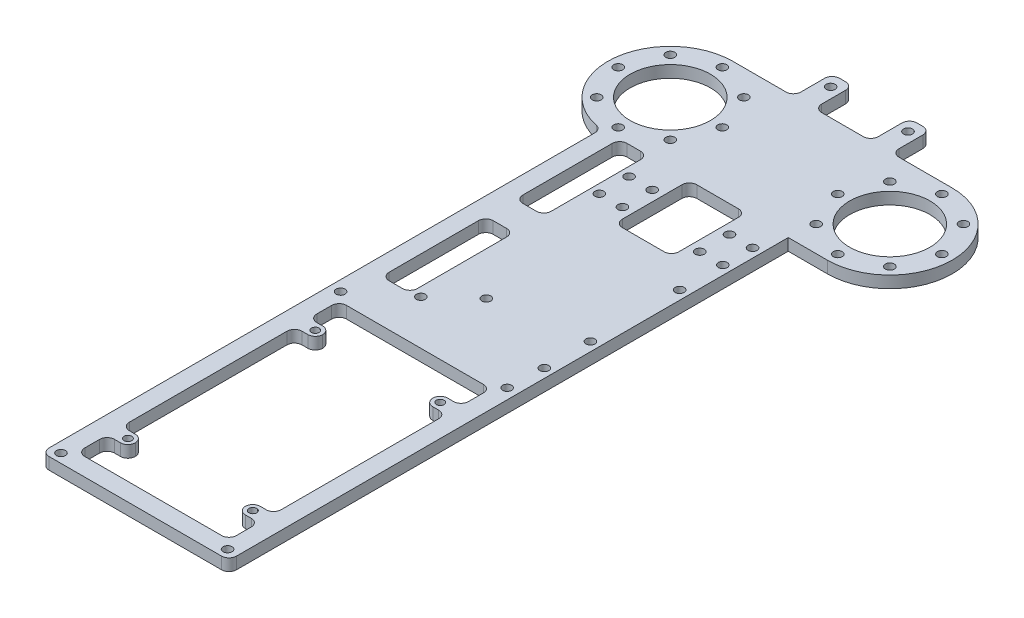
SolidWorks part; units mm, degrees
material "Thornel Mat VMA"
ref_plane "前视基准面" through (0, 0, 0) normal (0, 0, 1) x (1, 0, 0)
ref_plane "上视基准面" through (0, 0, 0) normal (0, 1, 0) x (1, 0, 0)
ref_plane "右视基准面" through (0, 0, 0) normal (1, 0, 0) x (0, 0, -1)
sketch "草图1" plane through (0, 0, 0) normal (0, 1, 0) x (1, 0, 0)
  line L0 (0, 0) -> (0, 103.5) construction
  line L1 (16.5, 103.5) -> (-16.5, 103.5)
  line L2 (-16.5, 103.5) -> (-16.5, 90.5)
  line L3 (-16.5, 90.5) -> (-36.9, 90.5)
  line L5 (-39.25, 48.6319) -> (-39.25, -39.5)
  line L6 (36.9, 48.5) -> (23.75, 48.5)
  line L7 (16.5, 90.5) -> (36.9, 90.5)
  line L8 (16.5, 103.5) -> (16.5, 90.5)
  line L9 (-13, 99.5) -> (-13, 39.5) construction
  line L10 (-36.9, 69.5) -> (-13, 69.5) construction
  line L11 (0, 0) -> (-39.25, 0) construction
  line L12 (-13, 39.5) -> (-13, 29.5) construction
  line L13 (-39.25, 24.5) -> (0, 24.5) construction
  line L14 (0, 0) -> (23.75, 0) construction
  line L15 (23.75, 34.5) -> (52.65, 34.5) construction
  line L16 (23.75, 34.5) -> (23.75, -34.5)
  line L17 (23.75, -34.5) -> (52.65, -34.5) construction
  line L18 (52.65, 34.5) -> (52.65, -34.5) construction
  line L19 (36.9, 39.5) -> (36.9, 34.5) construction
  line L20 (23.75, 48.5) -> (23.75, 34.5)
  line L21 (23.75, -34.5) -> (23.75, -39.5)
  line L23 (23.75, -39.5) -> (23.75, -139.5)
  line L24 (23.75, -139.5) -> (-39.25, -139.5)
  line L25 (-39.25, -139.5) -> (-39.25, -39.5)
  line L27 (-39.25, -39.5) -> (23.75, -39.5) construction
  line L28 (-7.75, -39.5) -> (-7.75, -139.5) construction
  line L29 (-39.25, -89.5) -> (-7.75, -89.5) construction
  line L30 (13, 39.5) -> (20.75, 39.5) construction
  line L31 (20.75, 39.5) -> (20.75, 29.5) construction
  line L32 (20.75, 29.5) -> (13, 29.5) construction
  line L33 (20.75, 29.5) -> (20.75, -30.5) construction
  arc A0 (-36.9, 90.5) -> (-39.25, 48.6319) centre (-36.9, 69.5) ccw
  arc A1 (36.9, 90.5) -> (36.9, 48.5) centre (36.9, 69.5) cw
  circle A2 centre (-36.9, 69.5) radius 13.5
  circle A3 centre (-36.9, 69.5) radius 17.5 construction
  circle A4 centre (-36.9, 87) radius 1.5
  circle A5 centre (-24.5256, 81.8744) radius 1.5
  circle A6 centre (-19.4, 69.5) radius 1.5
  circle A7 centre (-24.5256, 57.1256) radius 1.5
  circle A8 centre (-36.9, 52) radius 1.5
  circle A9 centre (-49.2744, 57.1256) radius 1.5
  circle A10 centre (-54.4, 69.5) radius 1.5
  circle A11 centre (-49.2744, 81.8744) radius 1.5
  circle A12 centre (-13, 99.5) radius 1.5
  circle A13 centre (-13, 39.5) radius 1.5
  circle A14 centre (-36.9, 69.5) radius 30 construction
  circle A15 centre (13, 39.5) radius 1.5
  circle A16 centre (13, 99.5) radius 1.5
  circle A17 centre (54.4, 69.5) radius 1.5
  circle A18 centre (49.2744, 57.1256) radius 1.5
  circle A19 centre (36.9, 52) radius 1.5
  circle A20 centre (24.5256, 57.1256) radius 1.5
  circle A21 centre (19.4, 69.5) radius 1.5
  circle A22 centre (24.5256, 81.8744) radius 1.5
  circle A23 centre (36.9, 87) radius 1.5
  circle A24 centre (49.2744, 81.8744) radius 1.5
  circle A25 centre (36.9, 69.5) radius 13.5
  circle A26 centre (-13, 29.5) radius 1.5
  circle A27 centre (36.9, 69.5) radius 30 construction
  circle A28 centre (-35.75, -42.5) radius 1.5
  circle A29 centre (-35.75, -136.5) radius 1.5
  circle A30 centre (20.25, -136.5) radius 1.5
  circle A31 centre (20.25, -42.5) radius 1.5
  circle A32 centre (13, 29.5) radius 1.5
  circle A33 centre (20.75, 15) radius 1.5
  circle A34 centre (20.75, -15) radius 1.5
  circle A35 centre (-28.75, -58) radius 1.3
  circle A36 centre (-28.75, -121) radius 1.3
  circle A37 centre (13.25, -121) radius 1.3
  circle A38 centre (13.25, -58) radius 1.3
  circle A39 centre (-9.25, -20) radius 1.5
  circle A40 centre (20.75, 39.5) radius 1.5
  circle A41 centre (-20.75, 39.5) radius 1.5
  circle A42 centre (20.75, 29.5) radius 1.5
  circle A43 centre (-20.75, 29.5) radius 1.5
  circle A44 centre (20.75, -30.5) radius 1.5
  circle A45 centre (-20.75, -30.5) radius 1.5
  point P37 (-36.9, 69.5)
  point P113 (0, 0)
  point P120 (0, 0)
  dimension "D2" = 27
  dimension "D3" = 3
  dimension "D5" = 35
  dimension "D6" = 60
  dimension "D7" = 3
  dimension "D9" = 26
  dimension "D10" = 4
  dimension "D12" = 10
  dimension "D13" = 5
  dimension "D21" = 3
  dimension "D22" = 94
  dimension "D23" = 56
  dimension "D24" = 3
  dimension "D25" = 30
  dimension "D26" = 3
  dimension "D27" = 21
  dimension "D19" = 42
  dimension "D29" = 63
  dimension "D30" = 2.6
  dimension "D31" = 5
  dimension "D32" = 30
  dimension "D33" = 3
  dimension "D34" = 3
  dimension "D1" = 73.8
  dimension "D8" = 60
  dimension "D11" = 33
  dimension "D14" = 5
  dimension "D15" = 69
  dimension "D16" = 28.9
  dimension "D17" = 5
  dimension "D18" = 100
  dimension "D20" = 52.65
  dimension "D28" = 63
  dimension "D36" = 60
  dimension "D35" = 2
  dimension "D4" = 8
extrude "凸台-拉伸1" add sketch "草图1" along normal blind 4
sketch "草图2" plane through (0, 4, 0) normal (0, 1, 0) x (1, 0, 0)
  line L0 (16.5, 103.5) -> (-16.5, 103.5) construction
  line L1 (-9.5, 103.5) -> (9.5, 103.5)
  line L2 (-9.5, 103.5) -> (-9.5, 90.5)
  line L3 (-9.5, 90.5) -> (9.5, 90.5)
  line L4 (9.5, 103.5) -> (9.5, 90.5)
  line L5 (-33.25, -45.5) -> (17.75, -45.5)
  line L6 (-33.25, 48.8196) -> (-23.75, 48.8196)
  line L7 (-33.25, 48.8196) -> (-33.25, 13.8196)
  line L8 (-33.25, 13.8196) -> (-23.75, 13.8196)
  line L9 (-23.75, 48.8196) -> (-23.75, 13.8196)
  line L10 (-33.25, 3.8196) -> (-23.75, 3.8196)
  line L11 (-33.25, 3.8196) -> (-33.25, -31.1804)
  line L12 (-33.25, -31.1804) -> (-23.75, -31.1804)
  line L13 (-23.75, 3.8196) -> (-23.75, -31.1804)
  line L18 (17.75, -45.5) -> (17.75, -55.5)
  line L19 (17.75, -55.5) -> (10.75, -55.5)
  line L20 (10.75, -55.5) -> (10.75, -60.5)
  line L21 (10.75, -60.5) -> (17.75, -60.5)
  line L22 (17.75, -60.5) -> (17.75, -118.5)
  line L23 (17.75, -55.5) -> (17.75, -60.5) construction
  line L24 (-35.75, -42.5) -> (-35.75, -136.5) construction
  line L25 (-7.75, -139.5) -> (-7.75, -89.5) construction
  line L26 (-39.25, -139.5) -> (23.75, -139.5) construction
  line L27 (-7.75, -89.5) -> (-35.75, -89.5) construction
  line L28 (-7.75, -45.5) -> (-7.75, -89.5) construction
  line L29 (-7.75, -89.5) -> (17.75, -89.5) construction
  line L30 (13.25, -58) -> (10.75, -58) construction
  line L31 (13.25, -58) -> (13.25, -55.5) construction
  line L32 (23.75, -139.5) -> (23.75, 48.5) construction
  line L33 (10.75, -118.5) -> (17.75, -118.5)
  line L34 (10.75, -123.5) -> (10.75, -118.5)
  line L35 (17.75, -123.5) -> (10.75, -123.5)
  line L36 (17.75, -133.5) -> (17.75, -123.5)
  line L37 (-33.25, -133.5) -> (17.75, -133.5)
  line L38 (-33.25, -45.5) -> (-33.25, -55.5)
  line L39 (-33.25, -55.5) -> (-26.25, -55.5)
  line L40 (-26.25, -55.5) -> (-26.25, -60.5)
  line L41 (-26.25, -60.5) -> (-33.25, -60.5)
  line L42 (-33.25, -60.5) -> (-33.25, -118.5)
  line L43 (-26.25, -118.5) -> (-33.25, -118.5)
  line L44 (-26.25, -123.5) -> (-26.25, -118.5)
  line L45 (-33.25, -123.5) -> (-26.25, -123.5)
  line L46 (-33.25, -133.5) -> (-33.25, -123.5)
  line L47 (-33.25, -45.5) -> (-33.25, -31.1804) construction
  line L48 (-33.25, 3.8196) -> (-33.25, 13.8196) construction
  line L49 (13, 39.5) -> (23.75, 39.5) construction
  line L50 (-13, 39.5) -> (-23.75, 39.5) construction
  line L52 (0, 90.5) -> (0, 0) construction
  line L53 (-16.5, 90.5) -> (-9.5, 90.5) construction
  line L54 (9.5, 48.5) -> (23.75, 48.5) construction
  line L55 (-9.5, 48.5) -> (9.5, 48.5)
  line L56 (-9.5, 48.5) -> (-9.5, 23.5)
  line L57 (-9.5, 23.5) -> (9.5, 23.5)
  line L58 (9.5, 48.5) -> (9.5, 23.5)
  line L59 (-13, 29.5) -> (-9.5, 29.5) construction
  line L60 (13, 29.5) -> (9.5, 29.5) construction
  circle A0 centre (-36.9, 69.5) radius 21 construction
  point P57 (-7.75, -133.5)
  dimension "D1" = 5
  dimension "D2" = 6
  dimension "D3" = 2.5
  dimension "D4" = 6
  dimension "D5" = 10
  dimension "D6" = 35
  dimension "D7" = 19
  dimension "D8" = 3.5
  dimension "D9" = 25
extrude "切除-拉伸1" cut sketch "草图2" against normal through all
fillet "圆角1" radius 2.5 43 edges at (23.75, 2, 139.5) (-39.25, 2, 139.5) (-33.25, 2, 123.5) (-26.25, 2, 123.5) (-33.25, 2, 118.5) (-26.25, 2, 118.5) (-33.25, 2, 133.5) (17.75, 2, 133.5) (17.75, 2, 123.5) (10.75, 2, 123.5) (10.75, 2, 118.5) (17.75, 2, 118.5) (17.75, 2, 55.5) (17.75, 2, 60.5) (10.75, 2, 60.5) (10.75, 2, 55.5) (-33.25, 2, 60.5) (-26.25, 2, 60.5) (-26.25, 2, 55.5) (-33.25, 2, 55.5) (17.75, 2, 45.5) (-33.25, 2, 45.5) (-33.25, 2, 31.1804) (-23.75, 2, 31.1804) (-23.75, 2, -13.8196) (-33.25, 2, -13.8196) (-23.75, 2, -3.8196) (-33.25, 2, -3.8196) (-33.25, 2, -48.8196) (-23.75, 2, -48.8196) (-39.25, 2, -48.6319) (-16.5, 2, -90.5) (9.5, 2, -90.5) (16.5, 2, -90.5) (16.5, 2, -103.5) (9.5, 2, -103.5) (-9.5, 2, -90.5) (-9.5, 2, -103.5) (-16.5, 2, -103.5) (-9.5, 2, -23.5) (9.5, 2, -23.5) (9.5, 2, -48.5) (-9.5, 2, -48.5)
